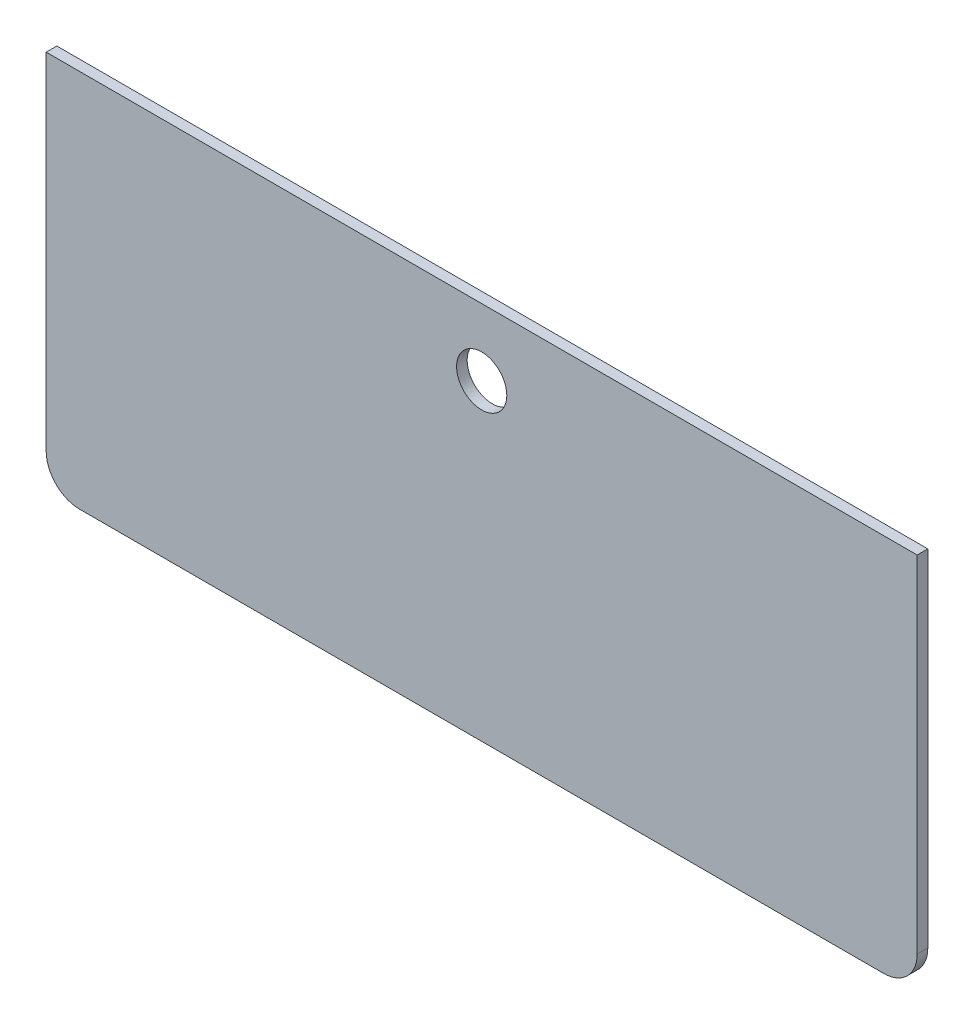
SolidWorks part; units mm, degrees
material "5052-H32"
ref_plane "Front Plane" through (0, 0, 0) normal (0, 0, 1) x (1, 0, 0)
ref_plane "Top Plane" through (0, 0, 0) normal (0, 1, 0) x (1, 0, 0)
ref_plane "Right Plane" through (0, 0, 0) normal (1, 0, 0) x (0, 0, -1)
sketch "Sketch1" plane through (0, 0, 0) normal (0, 0, 1) x (1, 0, 0)
  line L0 (-156.7654, 27.1868) -> (-156.7654, -85.9882)
  line L1 (-156.7654, -85.9882) -> (103.2346, -85.9882)
  line L2 (103.2346, -85.9882) -> (103.2346, 27.1868)
  line L3 (103.2346, 27.1868) -> (-156.7654, 27.1868)
  line L4 (-26.7654, 27.1868) -> (-26.7654, 7.1868) construction
  circle A0 centre (-26.7654, 7.1868) radius 7.5
  dimension "D4" = 15
  dimension "D1" = 113.175
  dimension "D2" = 260
  dimension "D3" = 20
extrude "Boss-Extrude1" add sketch "Sketch1" along normal blind 3.175
fillet "Fillet1" radius 10 2 edges at (-156.7654, -85.9882, 1.5875) (103.2346, -85.9882, 1.5875)
equation "\"L\"= 500"
equation "\"W\"= 260"
equation "\"H\"= 110"
equation "\"Compartment Width\"= 90"
equation "\"T\"= 4.7625 * 2 / 3"
equation "\"Inside Fillet Radius\"= 10"
equation "\"D1@Boss-Extrude1\"=\"T\""
equation "\"D1@Fillet1\"=\"Inside Fillet Radius\""
equation "\"Hole\"=15"
equation "\"D4@Sketch1\"=\"Hole\""
equation "\"D2@Sketch1\"=\"W\""
equation "\"D1@Sketch1\"=\"H\"+\"T\""
